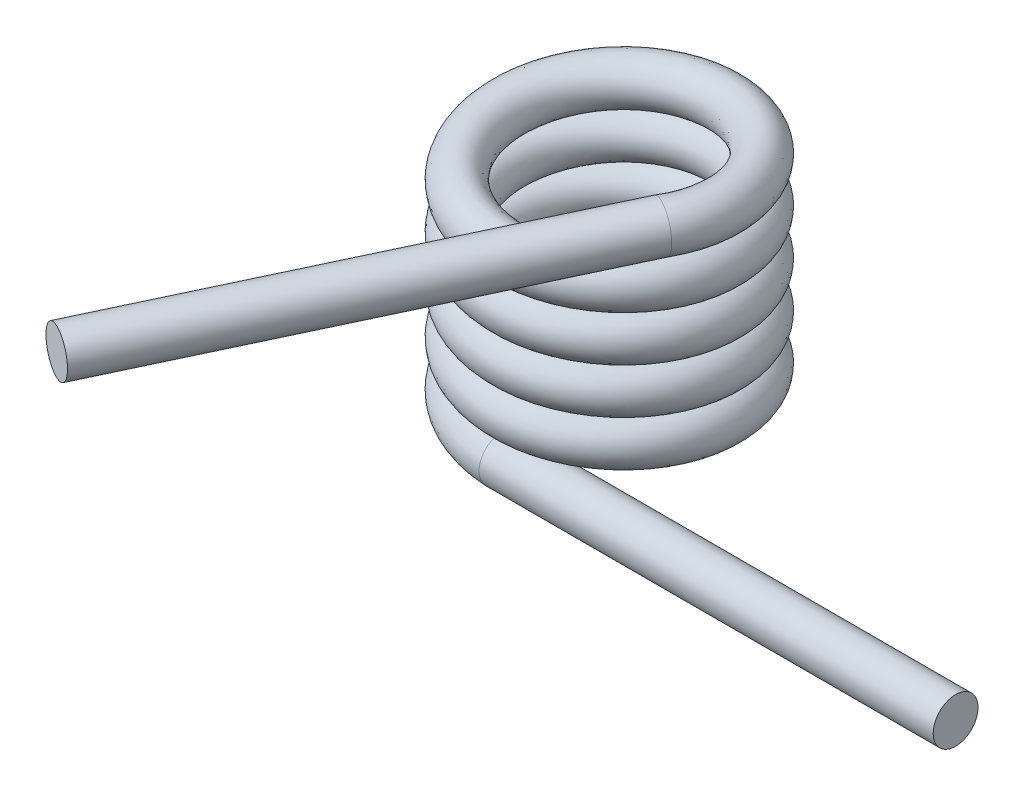
SolidWorks part; units mm, degrees
material "AISI 1020"
ref_plane "Спереди" through (0, 0, 0) normal (0, 0, 1) x (1, 0, 0)
ref_plane "Сверху" through (0, 0, 0) normal (0, 1, 0) x (1, 0, 0)
ref_plane "Справа" through (0, 0, 0) normal (1, 0, 0) x (0, 0, -1)
sketch "Эскиз1" plane through (0, 0, 0) normal (0, 1, 0) x (1, 0, 0)
  circle A0 centre (0, 0) radius 23 construction
  circle A1 centre (0, 0) radius 15 construction
  circle A2 centre (0, 0) radius 19
  dimension "D1" = 46
  dimension "D2" = 30
  dimension "D3" = 38
curve "Спираль1" pitch 8 height 38.56 radius 19 left hand yes centre (0, 0, 0) axis (0, 1, 0) start towards (0, 0, 1)
ref_plane "Плоскость1" through (0, 0, 0) normal (-1, 0, 0) x (0, 0, 1)
sketch "Эскиз2" plane through (0, 0, 0) normal (-1, 0, 0) x (0, 0, 1)
  circle A0 centre (19, 0) radius 3.95
  dimension "D1" = 7.9
sweep "По траектории1" add profiles "Эскиз2" path "Спираль1"
extrude "Бобышка-Вытянуть1" add sketch "Эскиз2<2>" against normal blind 80
sketch "Эскиз2<2>" plane through (0, 0, 0) normal (-1, 0, 0) x (0, 0, 1) same geometry as "Эскиз2"
sketch "Эскиз4" plane through (0, 0, 0) normal (-0.4258, 0, 0.9048) x (0.9048, 0, 0.4258)
  circle A0 centre (19, 38.5599) radius 3.95 construction
  circle A1 centre (19, 38.5599) radius 3.95
extrude "Бобышка-Вытянуть2" add sketch "Эскиз4" along normal blind 80
sketch "Эскиз5" plane through (0, 0, 0) normal (0, 1, 0) x (1, 0, 0)
  line L0 (0, -19) -> (80, -19)
  line L1 (0, 10.45) -> (0, -10.45) construction
  line L2 (17.1546, -8.1683) -> (-17.2383, -80.398)
  line L3 (80, -22.95) -> (80, -15.05) construction
  circle A0 centre (0, 0) radius 19
  dimension "D1" = 115
equation "\"D3@Эскиз1\"=(\"D2@Эскиз1\"+\"D1@Эскиз1\")/2"
